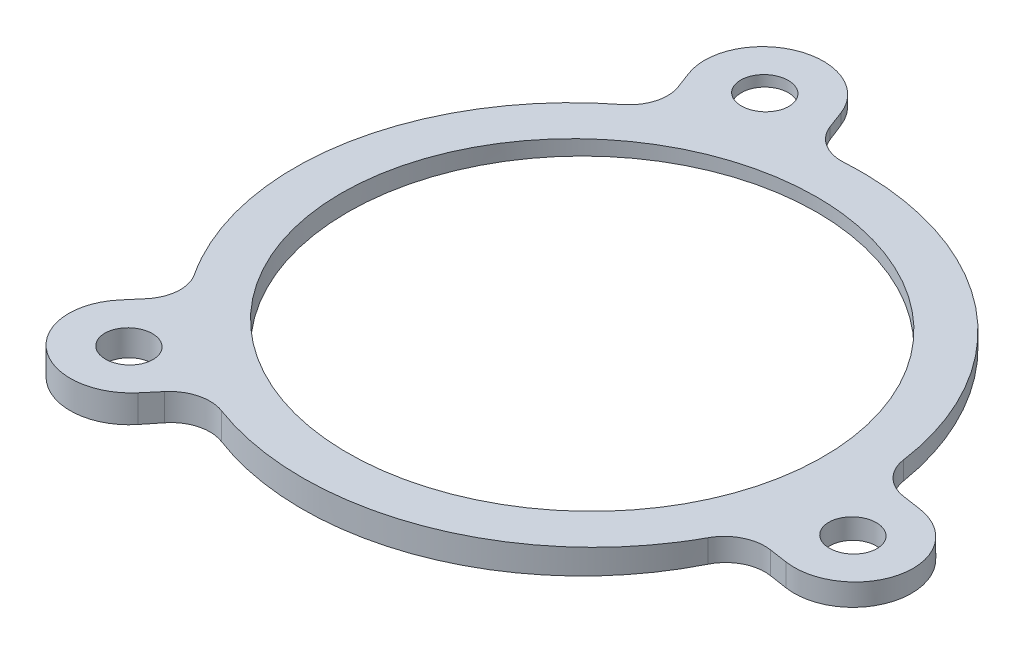
SolidWorks part; units mm, degrees
material "5454-O"
ref_plane "Front Plane" through (0, 0, 0) normal (0, 0, 1) x (1, 0, 0)
ref_plane "Top Plane" through (0, 0, 0) normal (0, 1, 0) x (1, 0, 0)
ref_plane "Right Plane" through (0, 0, 0) normal (1, 0, 0) x (0, 0, -1)
sketch "Sketch1" plane through (0, 0, 0) normal (0, 0, 1) x (1, 0, 0)
  line L0 (-3.7459, 1) -> (5.6477, 1) construction
  dimension "D1" = 1
ref_plane "Plane1" through (0, 0.9992, -0.0274) normal (0, 0.9996, -0.0274) x (1, 0, 0)
sketch "Sketch2" plane through (0, 0, 0) normal (0, 1, 0) x (1, 0, 0)
  line L0 (0, 0) -> (-6.0205, 15.3624) construction
  line L1 (0, 0) -> (-10.294, -12.8951) construction
  line L2 (0, 0) -> (16.3145, -2.4673) construction
  line L3 (-6.0205, 15.3624) -> (-3.2273, 16.4571) construction
  line L4 (-6.0205, 15.3624) -> (-8.8136, 14.2678) construction
  line L5 (-3.2273, 16.4571) -> (-2.3151, 14.1294) construction
  line L6 (-8.8136, 14.2678) -> (-7.9014, 11.9402) construction
  line L7 (16.3145, -2.4673) -> (16.7631, 0.4989) construction
  line L8 (16.3145, -2.4673) -> (15.8659, -5.4336) construction
  line L9 (16.7631, 0.4989) -> (14.2912, 0.8728) construction
  line L10 (15.8659, -5.4336) -> (13.394, -5.0598) construction
  line L11 (-10.294, -12.8951) -> (-7.9495, -14.7667) construction
  line L12 (-10.294, -12.8951) -> (-12.6386, -11.0234) construction
  line L13 (-12.6386, -11.0234) -> (-11.0789, -9.0696) construction
  line L14 (-7.9495, -14.7667) -> (-6.3898, -12.8129) construction
  line L15 (-8.8136, 14.2678) -> (-8.4608, 13.3674)
  line L16 (-3.2273, 16.4571) -> (-2.8744, 15.5566)
  line L17 (16.7631, 0.4989) -> (15.8069, 0.6436)
  line L18 (15.8659, -5.4336) -> (14.9097, -5.289)
  line L19 (-7.9495, -14.7667) -> (-7.3461, -14.0109)
  line L20 (-12.6386, -11.0234) -> (-12.0352, -10.2676)
  arc A0 (-8.8136, 14.2678) -> (-3.2273, 16.4571) centre (-6.0205, 15.3624) cw
  arc A1 (16.7631, 0.4989) -> (15.8659, -5.4336) centre (16.3145, -2.4673) cw
  arc A2 (-7.9495, -14.7667) -> (-12.6386, -11.0234) centre (-10.294, -12.8951) cw
  arc A3 (-0.8882, 14.2902) -> (14.1319, 2.2998) centre (0, 0) cw
  arc A4 (12.8198, -6.3759) -> (-5.0743, -13.3885) centre (0, 0) cw
  arc A5 (-11.9316, -7.9144) -> (-9.0576, 11.0887) centre (0, 0) cw
  arc A6 (-11.9316, -7.9144) -> (-12.0352, -10.2676) centre (-13.5983, -9.0199) cw
  arc A7 (12.8198, -6.3759) -> (14.9097, -5.289) centre (14.6106, -7.2665) cw
  arc A8 (-0.8882, 14.2902) -> (-2.8744, 15.5566) centre (-1.0123, 16.2864) cw
  arc A9 (-7.3461, -14.0109) -> (-5.0743, -13.3885) centre (-5.7831, -15.2587) cw
  arc A10 (15.8069, 0.6436) -> (14.1319, 2.2998) centre (16.1059, 2.6211) cw
  arc A11 (-9.0576, 11.0887) -> (-8.4608, 13.3674) centre (-10.3229, 12.6376) ccw
  circle A12 centre (0, 0) radius 12
  circle A13 centre (-6.0205, 15.3624) radius 1.2
  circle A14 centre (16.3145, -2.4673) radius 1.2
  circle A15 centre (-10.294, -12.8951) radius 1.2
  dimension "D1" = 2
  dimension "D2" = 2
extrude "Boss-Extrude1" add sketch "Sketch2" along normal up to surface (0.6089 mm away) up to plane "Plane1"
sketch3d "3DSketch3"
  point P0 (20.3145, 1.4981, -19.3624)
